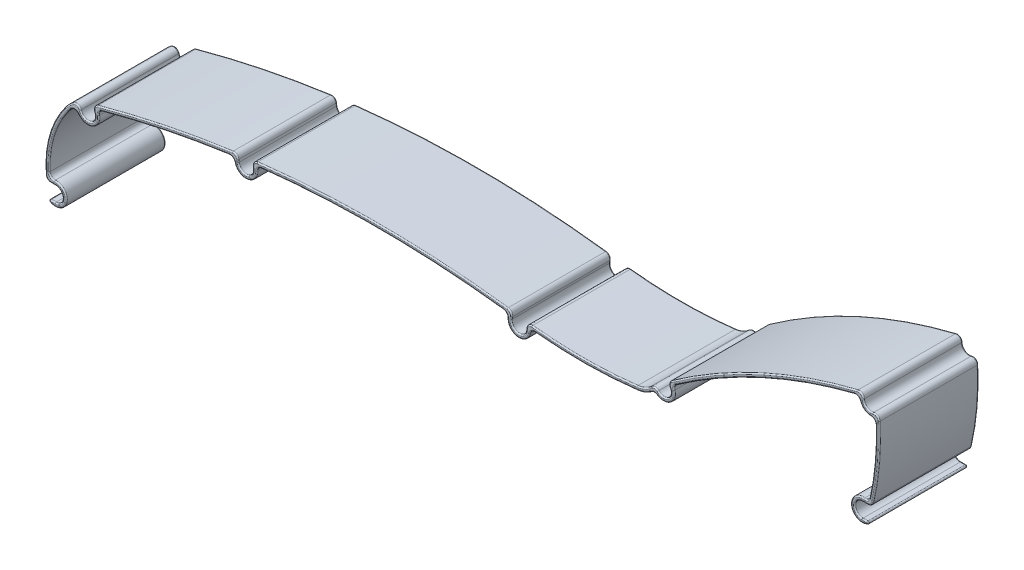
SolidWorks part; units mm, degrees
material "AR-M2"
ref_plane "正面" through (0, 0, 0) normal (0, 0, 1) x (1, 0, 0)
ref_plane "平面" through (0, 0, 0) normal (0, 1, 0) x (1, 0, 0)
ref_plane "右側面" through (0, 0, 0) normal (1, 0, 0) x (0, 0, -1)
sketch "ｽｹｯﾁ1" plane through (0, 0, 0) normal (0, 0, 1) x (1, 0, 0)
  line L0 (152.9752, 59.7355) -> (155.8598, 58.9115) construction
  line L2 (-22.5, -19) -> (22.5, -19)
  line L6 (150, 3) -> (150, 12)
  circle A0 centre (152.9752, 59.7355) radius 3 construction
  arc A25 (145.1217, 33.8719) -> (159.4857, 98.9896) centre (52.35, 88.479) ccw
  arc A26 (159.4857, 98.9896) -> (155.8531, 101.6261) centre (156.5, 98.6967) ccw
  arc A27 (155.8531, 101.6261) -> (74.5652, 65.2106) centre (203.2901, -113.1988) ccw
  arc A28 (73.7195, 65.056) -> (74.5652, 65.2106) centre (73.98, 66.0215) ccw
  arc A29 (73.7195, 65.056) -> (74.5652, 65.2106) centre (73.98, 66.0215) ccw
  arc A30 (73.7195, 65.056) -> (69.9392, 62.246) centre (72.938, 62.1596) ccw
  arc A31 (73.7195, 65.056) -> (69.9392, 62.246) centre (72.938, 62.1596) ccw
  arc A32 (62.3481, 57.6959) -> (67.3326, 59.7624) centre (61.1527, 67.6242) ccw
  arc A33 (15.0718, 58.0612) -> (62.3481, 57.6959) centre (40.1338, 242.1889) ccw
  arc A34 (15.0718, 58.0612) -> (-159.8291, 45.3832) centre (-42.29, -363.3692) ccw
  arc A35 (-159.8291, 45.3832) -> (-168.029, 39.7531) centre (-155.4945, 30.2837) ccw
  arc A36 (-168.029, 39.7531) -> (-174.9177, 6.802) centre (-136.5587, 15.9784) ccw
  arc A37 (-174.9177, 6.802) -> (-172, 4.5) centre (-172, 7.5) ccw
  arc A38 (-128.5711, -10.4869) -> (-172, 4.5) centre (-172, -65.9175) ccw
  arc A39 (-128.5711, -10.4869) -> (-89, -16.1206) centre (-103.9017, 21) ccw
  arc A40 (-24.2684, -18.5879) -> (-89, -16.1206) centre (-59.3978, -89.8605) ccw
  arc A41 (-24.2684, -18.5879) -> (-22.5, -19) centre (-22.5, -15) ccw
  arc A42 (95.4808, -24.1793) -> (22.5, -19) centre (22.5, -535.7727) ccw
  arc A43 (95.4808, -24.1793) -> (100, -24.5) centre (100, 7.5) ccw
  arc A44 (100, -24.5) -> (140.9896, -3.1331) centre (100, 25.5) ccw
  arc A45 (147, 0) -> (140.9896, -3.1331) centre (147, -7.3316) ccw
  arc A48 (69.5475, 61.4807) -> (69.9392, 62.246) centre (68.9396, 62.2747) ccw
  arc A49 (145.1217, 33.8719) -> (140.5409, 25.3936) centre (258.447, -32.8336) ccw
  arc A50 (155.8598, 58.9115) -> (159.4857, 98.9896) centre (52.35, 88.479) ccw
  arc A51 (159.4857, 98.9896) -> (155.8531, 101.6261) centre (156.5, 98.6967) ccw
  arc A52 (155.8531, 101.6261) -> (74.5652, 65.2106) centre (203.2901, -113.1988) ccw
  arc A53 (69.5475, 61.4807) -> (69.9392, 62.246) centre (68.9396, 62.2747) ccw
  arc A54 (69.5475, 61.4807) -> (67.3326, 59.7624) centre (203.2901, -113.1988) ccw
  arc A55 (69.5475, 61.4807) -> (67.3326, 59.7624) centre (203.2901, -113.1988) ccw
  arc A56 (140.5409, 25.3936) -> (147, 15) centre (147, 22.2038) ccw
  arc A57 (62.3481, 57.6959) -> (67.3326, 59.7624) centre (61.1527, 67.6242) ccw
  arc A58 (15.0718, 58.0612) -> (62.3481, 57.6959) centre (40.1338, 242.1889) ccw
  arc A59 (15.0718, 58.0612) -> (-159.8291, 45.3832) centre (-42.29, -363.3692) ccw
  arc A60 (-159.8291, 45.3832) -> (-168.029, 39.7531) centre (-155.4945, 30.2837) ccw
  arc A61 (-168.029, 39.7531) -> (-174.9177, 6.802) centre (-136.5587, 15.9784) ccw
  arc A86 (147, 0) -> (150, 3) centre (147, 3) ccw
  arc A87 (150, 12) -> (147, 15) centre (147, 12) ccw
  dimension "D1" = 0
extrude "押し出し-薄板1" add sketch "ｽｹｯﾁ1" along normal up to surface (40 mm away) thin thin type one direction reverse wall 1.5
sketch "ｽｹｯﾁ2" plane through (0, 0, 0) normal (0, 0, 1) x (1, 0, 0)
  circle A0 centre (156.5, 98.6967) radius 3 construction
  circle A1 centre (152.9752, 59.7355) radius 3 construction
  circle A2 centre (72.938, 62.1596) radius 3 construction
  circle A3 centre (14.6672, 55.0886) radius 3 construction
  circle A4 centre (-95.3328, 55.6027) radius 3 construction
  circle A5 centre (-159, 42.5) radius 3 construction
  circle A6 centre (-172, 7.5) radius 3 construction
  circle A7 centre (156.5, 98.6967) radius 3
  circle A8 centre (152.9752, 59.7355) radius 3
  circle A9 centre (72.938, 62.1596) radius 3
  circle A10 centre (14.6672, 55.0886) radius 3
  circle A11 centre (-95.3328, 55.6027) radius 3
  circle A12 centre (-159, 42.5) radius 3
  circle A13 centre (-172, 7.5) radius 3
extrude "ﾎﾞｽ - 押し出し1" add sketch "ｽｹｯﾁ2" along normal through all
sketch "ｽｹｯﾁ3" plane through (0, 0, 40) normal (0, 0, 1) x (1, 0, 0)
  circle A0 centre (-172, 7.5) radius 4.5
  circle A1 centre (-159, 42.5) radius 4.5
  circle A2 centre (-95.3328, 55.6027) radius 4.5
  circle A3 centre (14.6672, 55.0886) radius 4.5
  circle A4 centre (72.938, 62.1596) radius 4.5
  circle A5 centre (156.5, 98.6967) radius 4.5
  circle A6 centre (152.9752, 59.7355) radius 4.5
  arc A17 (-168.029, 39.7531) -> (-174.9177, 6.802) centre (-136.5587, 15.9784) ccw
  arc A18 (-168.029, 39.7531) -> (-174.9177, 6.802) centre (-136.5587, 15.9784) ccw
  arc A19 (-174.9177, 6.802) -> (-173.9852, 9.7492) centre (-172, 7.5) ccw
  arc A20 (-174.9177, 6.802) -> (-173.9852, 9.7492) centre (-172, 7.5) ccw
  arc A41 (-166.8321, 38.8489) -> (-173.9852, 9.7492) centre (-136.5587, 15.9784) ccw
  arc A42 (-166.8321, 38.8489) -> (-173.9852, 9.7492) centre (-136.5587, 15.9784) ccw
  arc A43 (-161.9687, 42.9324) -> (-166.8321, 38.8489) centre (-155.4945, 30.2837) ccw
  arc A44 (-161.9687, 42.9324) -> (-166.8321, 38.8489) centre (-155.4945, 30.2837) ccw
  arc A45 (-161.9687, 42.9324) -> (-156.911, 44.6532) centre (-159, 42.5) ccw
  arc A46 (17.4359, 56.2436) -> (62.5274, 56.2067) centre (40.1338, 242.1889) ccw
  arc A47 (62.5274, 56.2067) -> (68.2596, 58.5831) centre (61.1527, 67.6242) ccw
  arc A48 (70.4594, 60.2897) -> (68.2596, 58.5831) centre (203.2901, -113.1988) ccw
  arc A49 (70.4594, 60.2897) -> (70.5413, 60.3552) centre (68.9396, 62.2747) ccw
  arc A50 (-161.9687, 42.9324) -> (-156.911, 44.6532) centre (-159, 42.5) ccw
  arc A51 (-98.1023, 56.756) -> (-156.911, 44.6532) centre (-42.29, -363.3692) ccw
  arc A52 (-98.1023, 56.756) -> (-156.911, 44.6532) centre (-42.29, -363.3692) ccw
  arc A53 (-98.1023, 56.756) -> (-92.9382, 57.4098) centre (-95.3328, 55.6027) ccw
  arc A54 (-98.1023, 56.756) -> (-92.9382, 57.4098) centre (-95.3328, 55.6027) ccw
  arc A55 (12.2895, 56.918) -> (-92.9382, 57.4098) centre (-42.29, -363.3692) ccw
  arc A56 (12.2895, 56.918) -> (-92.9382, 57.4098) centre (-42.29, -363.3692) ccw
  arc A57 (12.2895, 56.918) -> (17.4359, 56.2436) centre (14.6672, 55.0886) ccw
  arc A58 (12.2895, 56.918) -> (17.4359, 56.2436) centre (14.6672, 55.0886) ccw
  arc A59 (70.5413, 60.3552) -> (75.3565, 63.9346) centre (72.938, 62.1596) ccw
  arc A60 (70.5413, 60.3552) -> (75.3565, 63.9346) centre (72.938, 62.1596) ccw
  arc A61 (69.5475, 61.4807) -> (69.9392, 62.246) centre (68.9396, 62.2747) ccw
  arc A62 (69.5475, 61.4807) -> (67.3326, 59.7624) centre (203.2901, -113.1988) ccw
  arc A63 (62.3481, 57.6959) -> (67.3326, 59.7624) centre (61.1527, 67.6242) ccw
  arc A64 (15.0718, 58.0612) -> (62.3481, 57.6959) centre (40.1338, 242.1889) ccw
  arc A65 (75.3565, 63.9346) -> (75.4428, 63.9941) centre (73.98, 66.0215) ccw
  arc A66 (75.3565, 63.9346) -> (75.4428, 63.9941) centre (73.98, 66.0215) ccw
  arc A67 (153.6343, 99.5841) -> (75.4428, 63.9941) centre (203.2901, -113.1988) ccw
  arc A68 (153.6343, 99.5841) -> (75.4428, 63.9941) centre (203.2901, -113.1988) ccw
  arc A69 (153.6343, 99.5841) -> (158.2162, 96.236) centre (156.5, 98.6967) ccw
  arc A70 (153.6343, 99.5841) -> (158.2162, 96.236) centre (156.5, 98.6967) ccw
  arc A71 (155.1051, 61.8482) -> (158.2162, 96.236) centre (52.35, 88.479) ccw
  arc A72 (155.1051, 61.8482) -> (158.2162, 96.236) centre (52.35, 88.479) ccw
  arc A73 (155.1051, 61.8482) -> (155.8598, 58.9115) centre (152.9752, 59.7355) ccw
  arc A74 (155.1051, 61.8482) -> (155.8598, 58.9115) centre (152.9752, 59.7355) ccw
  arc A75 (155.8598, 58.9115) -> (159.4857, 98.9896) centre (52.35, 88.479) ccw
  arc A76 (17.4359, 56.2436) -> (62.5274, 56.2067) centre (40.1338, 242.1889) ccw
  arc A77 (62.5274, 56.2067) -> (68.2596, 58.5831) centre (61.1527, 67.6242) ccw
  arc A78 (70.4594, 60.2897) -> (68.2596, 58.5831) centre (203.2901, -113.1988) ccw
  arc A79 (70.4594, 60.2897) -> (70.5413, 60.3552) centre (68.9396, 62.2747) ccw
  arc A80 (155.8598, 58.9115) -> (159.4857, 98.9896) centre (52.35, 88.479) ccw
  arc A81 (159.4857, 98.9896) -> (155.8531, 101.6261) centre (156.5, 98.6967) ccw
  arc A82 (159.4857, 98.9896) -> (155.8531, 101.6261) centre (156.5, 98.6967) ccw
  arc A83 (155.8531, 101.6261) -> (74.5652, 65.2106) centre (203.2901, -113.1988) ccw
  arc A84 (155.8531, 101.6261) -> (74.5652, 65.2106) centre (203.2901, -113.1988) ccw
  arc A85 (73.7195, 65.056) -> (74.5652, 65.2106) centre (73.98, 66.0215) ccw
  arc A86 (73.7195, 65.056) -> (74.5652, 65.2106) centre (73.98, 66.0215) ccw
  arc A87 (73.7195, 65.056) -> (69.9392, 62.246) centre (72.938, 62.1596) ccw
  arc A88 (73.7195, 65.056) -> (69.9392, 62.246) centre (72.938, 62.1596) ccw
  arc A89 (15.0718, 58.0612) -> (-159.8291, 45.3832) centre (-42.29, -363.3692) ccw
  arc A90 (15.0718, 58.0612) -> (-159.8291, 45.3832) centre (-42.29, -363.3692) ccw
  arc A91 (69.5475, 61.4807) -> (69.9392, 62.246) centre (68.9396, 62.2747) ccw
  arc A92 (69.5475, 61.4807) -> (67.3326, 59.7624) centre (203.2901, -113.1988) ccw
  arc A93 (62.3481, 57.6959) -> (67.3326, 59.7624) centre (61.1527, 67.6242) ccw
  arc A94 (15.0718, 58.0612) -> (62.3481, 57.6959) centre (40.1338, 242.1889) ccw
  arc A95 (-159.8291, 45.3832) -> (-168.029, 39.7531) centre (-155.4945, 30.2837) ccw
  arc A96 (-159.8291, 45.3832) -> (-168.029, 39.7531) centre (-155.4945, 30.2837) ccw
  arc M31 (-168.029, 39.7531) -> (-174.9177, 6.802) centre (-136.5587, 15.9784) ccw
  arc M32 (-174.9177, 6.802) -> (-173.9852, 9.7492) centre (-172, 7.5) ccw
  arc M33 (-173.9852, 9.7492) -> (-166.8321, 38.8489) centre (-136.5587, 15.9784) cw
  arc M34 (-166.8321, 38.8489) -> (-161.9687, 42.9324) centre (-155.4945, 30.2837) cw
  arc M35 (-161.9687, 42.9324) -> (-156.911, 44.6532) centre (-159, 42.5) ccw
  arc M36 (-156.911, 44.6532) -> (-98.1023, 56.756) centre (-42.29, -363.3692) cw
  arc M37 (-98.1023, 56.756) -> (-92.9382, 57.4098) centre (-95.3328, 55.6027) ccw
  arc M38 (-92.9382, 57.4098) -> (12.2895, 56.918) centre (-42.29, -363.3692) cw
  arc M39 (12.2895, 56.918) -> (17.4359, 56.2436) centre (14.6672, 55.0886) ccw
  arc M40 (17.4359, 56.2436) -> (62.5274, 56.2067) centre (40.1338, 242.1889) ccw
  arc M42 (68.2596, 58.5831) -> (70.4594, 60.2897) centre (203.2901, -113.1988) cw
  arc M43 (70.4594, 60.2897) -> (70.5413, 60.3552) centre (68.9396, 62.2747) ccw
  arc M44 (70.5413, 60.3552) -> (75.3565, 63.9346) centre (72.938, 62.1596) ccw
  arc M45 (75.3565, 63.9346) -> (75.4428, 63.9941) centre (73.98, 66.0215) ccw
  arc M46 (75.4428, 63.9941) -> (153.6343, 99.5841) centre (203.2901, -113.1988) cw
  arc M47 (153.6343, 99.5841) -> (158.2162, 96.236) centre (156.5, 98.6967) ccw
  arc M48 (158.2162, 96.236) -> (155.1051, 61.8482) centre (52.35, 88.479) cw
  arc M49 (155.1051, 61.8482) -> (155.8598, 58.9115) centre (152.9752, 59.7355) ccw
  arc M50 (155.8598, 58.9115) -> (159.4857, 98.9896) centre (52.35, 88.479) ccw
  dimension "D1" = 9
  dimension "D2" = 0
extrude "ﾎﾞｽ - 押し出し2" add sketch "ｽｹｯﾁ3" against normal through all contours A6 M48 M50 M49 | A5 M46 M48 M47 | A4 M42 M46 M45 M44 M43 | A3 M38 M40 M39 | A2 M36 M38 M37 | A1 M34 M36 M35 | A0 M31 M33 M32 region at (-173.3991, 3.3572, 40) region at (-162.678, 42.4107, 40) region at (-98.9039, 56.5367, 40) region at (11.4584, 56.9129, 40) region at (69.9721, 59.7793, 40) region at (154.707, 96.2487, 40) region at (155.1864, 62.6817, 40)
sketch "ｽｹｯﾁ4" plane through (0, 0, 40) normal (0, 0, 1) x (1, 0, 0)
  line L0 (-159, 42.5) -> (-159.8361, 45.3811) construction
  line L1 (-161.8811, 41.6639) -> (-162.7173, 44.545)
  line L2 (-156.1189, 43.3361) -> (-156.955, 46.2173)
  line L3 (-172, 7.5) -> (-176.5, 7.5) construction
  line L4 (-172, 4.5) -> (-176.5, 4.5)
  line L5 (-172, 10.5) -> (-176.5, 10.5)
  line L6 (-95.3328, 55.6027) -> (-95.7096, 58.579) construction
  line L7 (-98.3091, 55.2259) -> (-98.6859, 58.2022)
  line L8 (-92.3566, 55.9795) -> (-92.7334, 58.9558)
  line L9 (14.6672, 55.0886) -> (15.0718, 58.0612) construction
  line L10 (11.6946, 55.4932) -> (12.0992, 58.4658)
  line L11 (17.6397, 54.684) -> (18.0444, 57.6566)
  line L12 (72.938, 62.1596) -> (71.1482, 64.5673) construction
  line L13 (70.5303, 60.3699) -> (68.7406, 62.7776)
  line L14 (75.3456, 63.9494) -> (73.5559, 66.357)
  line L15 (156.5, 98.6967) -> (158.2622, 101.1246) construction
  line L16 (154.0721, 100.4589) -> (155.8343, 102.8868)
  line L17 (158.9279, 96.9345) -> (160.6901, 99.3624)
  line L18 (152.9752, 59.7355) -> (157.4752, 59.7355) construction
  line L19 (152.9752, 62.7355) -> (157.4752, 62.7355)
  line L20 (152.9752, 56.7355) -> (157.4752, 56.7355)
  line L21 (-99.735, 56.5359) -> (-91.3021, 57.6035) construction
  arc A0 (15.0718, 58.0612) -> (-159.8291, 45.3832) centre (-42.29, -363.3692) ccw construction
  arc A1 (-159.8291, 45.3832) -> (-168.029, 39.7531) centre (-155.4945, 30.2837) ccw construction
  arc A2 (-161.8811, 41.6639) -> (-156.1189, 43.3361) centre (-159, 42.5) ccw
  arc A3 (-156.955, 46.2173) -> (-162.7173, 44.545) centre (-159.8361, 45.3811) ccw
  arc A4 (-172, 4.5) -> (-172, 10.5) centre (-172, 7.5) ccw
  arc A5 (-176.5, 10.5) -> (-176.5, 4.5) centre (-176.5, 7.5) ccw
  arc A6 (-98.3091, 55.2259) -> (-92.3566, 55.9795) centre (-95.3328, 55.6027) ccw
  arc A7 (-92.7334, 58.9558) -> (-98.6859, 58.2022) centre (-95.7096, 58.579) ccw
  arc A8 (15.0718, 58.0612) -> (62.3481, 57.6959) centre (40.1338, 242.1889) ccw construction
  arc A9 (11.6946, 55.4932) -> (17.6397, 54.684) centre (14.6672, 55.0886) ccw
  arc A10 (18.0444, 57.6566) -> (12.0992, 58.4658) centre (15.0718, 58.0612) ccw
  circle A11 centre (72.938, 62.1596) radius 3 construction
  arc A12 (70.5303, 60.3699) -> (75.3456, 63.9494) centre (72.938, 62.1596) ccw
  arc A13 (73.5559, 66.357) -> (68.7406, 62.7776) centre (71.1482, 64.5673) ccw
  circle A14 centre (156.5, 98.6967) radius 3 construction
  arc A15 (154.0721, 100.4589) -> (158.9279, 96.9345) centre (156.5, 98.6967) ccw
  arc A16 (160.6901, 99.3624) -> (155.8343, 102.8868) centre (158.2622, 101.1246) ccw
  arc A17 (155.5082, 63.4549) -> (156.7424, 62.1969) centre (152.9752, 59.7355) ccw construction
  arc A18 (152.9752, 62.7355) -> (152.9752, 56.7355) centre (152.9752, 59.7355) ccw
  arc A19 (157.4752, 56.7355) -> (157.4752, 62.7355) centre (157.4752, 59.7355) ccw
  arc A20 (-175.5786, 10.2283) -> (-174.2242, 11.4119) centre (-172, 7.5) ccw construction
  point P12 (-159.4181, 43.9406)
  point P19 (-174.25, 7.5)
  point P29 (-95.5212, 57.0909)
  point P37 (14.8695, 56.5749)
  point P48 (72.0431, 63.3635)
  point P59 (157.3811, 99.9106)
  point P70 (155.2252, 59.7355)
  dimension "D1" = 6
extrude "ｶｯﾄ - 押し出し2" cut sketch "ｽｹｯﾁ4" against normal through all
fillet "ﾌｨﾚｯﾄ1" radius 2 24 edges at (-174.2242, 11.4119, 20) (-155.3241, 45.0957, 20) (-99.735, 56.5359, 20) (-91.3021, 57.6035, 20) (10.6553, 57.127, 20) (19.0628, 56.0522, 20) (69.3543, 59.438, 20) (76.5769, 64.8069, 20) (152.0286, 99.203, 20) (158.3244, 94.5831, 20) (155.5082, 63.4549, 20) (156.8765, 62.7355, 20) (159.5915, 97.8487, 20) (154.7384, 101.3769, 20) (74.4582, 65.1432, 20) (69.6428, 61.5638, 20) (18.0475, 57.6806, 20) (12.0977, 58.4553, 20) (-92.7321, 58.9453, 20) (-98.6846, 58.1917, 20) (-156.95, 46.2001, 20) (-162.6387, 44.2745, 20) (-175.6177, 10.5, 20) (-163.4764, 42.0393, 20)
fillet "ﾌｨﾚｯﾄ3" radius 0.5 2 edges at (156.3293, 56.7355, 20) (-175.3541, 4.5, 20)
fillet "ﾌｨﾚｯﾄ4" radius 0.5 134 edges at (149.9752, 59.7355, 0) (154.1363, 62.7355, 0) (156.5426, 63.1705, 0) (159.5859, 79.0461, 0) (159.0267, 95.5112, 0) (154.7232, 96.2795, 0) (152.7152, 100.1504, 0) (111.9498, 86.9435, 0) (75.3032, 65.1007, 0) (74.7277, 59.752, 0) (69.44, 60.7423, 0) (67.6924, 60.0446, 0) (64.9824, 58.3866, 0) (41.1719, 56.3663, 0) (18.5337, 57.0468, 0) (17.7117, 55.2124, 0) (14.2625, 52.116, 0) (11.76, 55.974, 0) (11.4286, 57.9445, 0) (-40.302, 61.9424, 0) (-92.0677, 58.4282, 0) (-92.4175, 56.4609, 0) (-94.956, 52.6265, 0) (-98.37, 55.7073, 0) (-99.1991, 57.5254, 0) (-128.0248, 53.2163, 0) (-156.2106, 45.7903, 0) (-156.2524, 43.7963, 0) (-158.1639, 39.6189, 0) (-161.891, 41.6978, 0) (-163.1966, 43.0742, 0) (-166.6348, 41.3596, 0) (-174.4968, 26.7635, 0) (-175.185, 11.0216, 0) (-172.919, 10.5, 0) (-169, 7.5, 0) (-172.9682, 4.5, 0) (-174.4206, 4.125, 0) (-167.6069, 6.5248, 0) (-173.7686, 12.4857, 0) (-172.8528, 27.0365, 0) (-166.3071, 39.5028, 0) (-164.1538, 40.734, 0) (-157.2222, 38.3661, 0) (-154.323, 44.8162, 0) (-127.7213, 51.7473, 0) (-100.5444, 55.8838, 0) (-94.7676, 51.1384, 0) (-90.3558, 57.1737, 0) (-40.309, 60.4424, 0) (9.705, 56.706, 0) (14.1156, 50.6225, 0) (19.8537, 55.4356, 0) (41.8972, 54.8717, 0) (65.4296, 56.9491, 0) (69.2025, 58.814, 0) (75.6214, 58.5473, 0) (77.2276, 64.7931, 0) (112.4002, 85.5002, 0) (151.2798, 98.4666, 0) (153.8276, 95.0762, 0) (157.8297, 93.6291, 0) (158.0682, 78.9148, 0) (155.1928, 64.4822, 0) (148.5382, 58.985, 0) (155.3958, 56.3605, 0) (153.9435, 56.7355, 0) (155.1928, 64.4822, 40) (158.0682, 78.9148, 40) (157.8297, 93.6291, 40) (153.8276, 95.0762, 40) (151.2798, 98.4666, 40) (112.4002, 85.5002, 40) (77.2276, 64.7931, 40) (75.6214, 58.5473, 40) (69.2025, 58.814, 40) (65.4296, 56.9491, 40) (41.8972, 54.8717, 40) (19.8537, 55.4356, 40) (14.1156, 50.6225, 40) (9.705, 56.706, 40) (-40.309, 60.4424, 40) (-90.3558, 57.1737, 40) (-94.7676, 51.1384, 40) (-100.5444, 55.8838, 40) (-127.7213, 51.7473, 40) (-154.323, 44.8162, 40) (-157.2222, 38.3661, 40) (-164.1538, 40.734, 40) (-166.3071, 39.5028, 40) (-172.8528, 27.0365, 40) (-173.7686, 12.4857, 40) (-167.6069, 6.5248, 40) (-174.4206, 4.125, 40) (-172.9682, 4.5, 40) (-169, 7.5, 40) (-172.919, 10.5, 40) (-175.185, 11.0216, 40) (-174.4968, 26.7635, 40) (-166.6348, 41.3596, 40) (-163.1966, 43.0742, 40) (-161.891, 41.6978, 40) (-158.1639, 39.6189, 40) (-156.2524, 43.7963, 40) (-156.2106, 45.7903, 40) (-128.0248, 53.2163, 40) (-99.1991, 57.5254, 40) (-98.37, 55.7073, 40) (-94.956, 52.6265, 40) (-92.4175, 56.4609, 40) (-92.0677, 58.4282, 40) (-40.302, 61.9424, 40) (11.4286, 57.9445, 40) (11.76, 55.974, 40) (14.2625, 52.116, 40) (17.7117, 55.2124, 40) (18.5337, 57.0468, 40) (41.1719, 56.3663, 40) (64.9824, 58.3866, 40) (67.6924, 60.0446, 40) (69.44, 60.7423, 40) (74.7277, 59.752, 40) (75.3032, 65.1007, 40) (111.9498, 86.9435, 40) (152.7152, 100.1504, 40) (154.7232, 96.2795, 40) (159.0267, 95.5112, 40) (159.5859, 79.0461, 40) (156.5426, 63.1705, 40) (154.1363, 62.7355, 40) (149.9752, 59.7355, 40) (153.9435, 56.7355, 40) (155.3958, 56.3605, 40) (148.5382, 58.985, 40)
